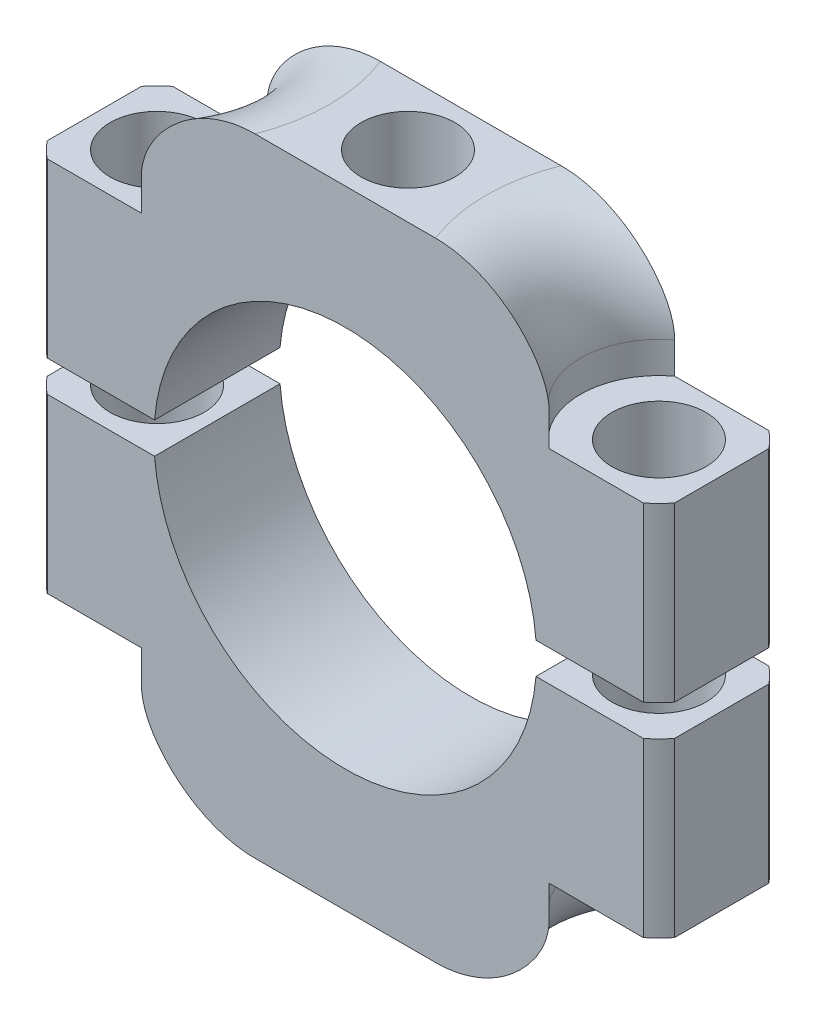
SolidWorks part; units mm, degrees
ref_plane "Front Plane" through (0, 0, 0) normal (0, 0, 1) x (1, 0, 0)
ref_plane "Top Plane" through (0, 0, 0) normal (0, 1, 0) x (1, 0, 0)
ref_plane "Right Plane" through (0, 0, 0) normal (1, 0, 0) x (0, 0, -1)
sketch "Sketch1" plane through (0, 0, 0) normal (0, 0, 1) x (1, 0, 0)
  line L1 (-10, -10) -> (10, -10)
  line L2 (-10, -10) -> (-10, 10)
  line L3 (-10, 10) -> (10, 10)
  line L4 (10, -10) -> (10, 10)
  line L5 (-10, -10) -> (10, 10) construction
  line L6 (-10, 10) -> (10, -10) construction
  line L7 (-10, -0.5) -> (-6.0795, -0.5)
  line L8 (-10, -0.5) -> (-10, 0.5)
  line L9 (-10, 0.5) -> (-6.0795, 0.5)
  line L10 (-6.0795, -0.5) -> (-6.0795, 0.5)
  line L11 (6.0795, -0.5) -> (10, -0.5)
  line L12 (6.0795, -0.5) -> (6.0795, 0.5)
  line L13 (6.0795, 0.5) -> (10, 0.5)
  line L14 (10, -0.5) -> (10, 0.5)
  circle A0 centre (0, 0) radius 6.1
  point P0 (0, 0)
  point P12 (6.0795, 0)
  point P13 (-6.0795, 0)
  dimension "D3" = 12.2
  dimension "D1" = 20
  dimension "D2" = 20
  dimension "D4" = 1
  dimension "D5" = 1
extrude "Boss-Extrude1" add sketch "Sketch1" along normal blind 4 contours A0 L7 L2 L1 L4 L11 | A0 L13 L4 L3 L2 L9 region at (0, -6.1587, 0) region at (0, 6.1587, 0)
sketch "Sketch2" plane through (0, 0, 0) normal (0, 1, 0) x (1, 0, 0)
  line L0 (10, -4) -> (10, 0) construction
  line L1 (-10, -4) -> (-10, 0) construction
  line L2 (0, 5.2223) -> (0, -8.4062) construction
  line L3 (-2.6121, 0) -> (-2.6121, -4)
  line L4 (-14.9471, -1.5628) -> (14.9628, -1.5628) construction
  line L5 (-10, 0) -> (10, 0) construction
  line L6 (-10, -4) -> (10, -4) construction
  circle A0 centre (8, -2) radius 2.5
  circle A1 centre (-8, -2) radius 2.5
  circle A2 centre (8, -2) radius 1.5
  circle A3 centre (-8, -2) radius 1.5
  point P21 (0, 0)
  point P22 (0, 0)
  dimension "D1" = 5
  dimension "D2" = 5
  dimension "D3" = 3
  dimension "D4" = 3
  dimension "D6" = 2
  dimension "D5" = 2
  dimension "D7" = 2
extrude "Cut-Extrude1" cut sketch "Sketch2" along direction (0, 1, 0) on the side of the normal blind 4 from surface contours A1 | A0 | A3 starting at face at (0, -10, 2)
sketch "Sketch3" plane through (0, 0, 0) normal (0, 1, 0) x (1, 0, 0)
  line L0 (0, 0) -> (0, -4)
  line L1 (-10, 0) -> (10, 0) construction
  line L2 (-10, -4) -> (-10, 0) construction
  line L3 (10, -4) -> (10, 0) construction
  circle A0 centre (8, -2) radius 2.5
  circle A1 centre (-8, -2) radius 2.5
  circle A2 centre (8, -2) radius 1.5
  circle A3 centre (-8, -2) radius 1.5
  point P8 (0, 0)
  point P11 (0, 0)
  point P12 (0, 0)
  point P13 (0, -2)
  dimension "D1" = 5
  dimension "D2" = 5
  dimension "D3" = 3
  dimension "D4" = 3
  dimension "D5" = 2
  dimension "D6" = 2
  dimension "D7" = 4
extrude "Cut-Extrude2" cut sketch "Sketch3" against normal blind 4 from surface contours A1 A3 | A0 A2 region at (5.5707, 0, 2) region at (-10.4293, 0, 2) starting at face at (0, 10, 2)
sketch "Sketch4" plane through (0, 10, 0) normal (0, 1, 0) x (1, 0, 0)
  line L0 (-10, -3.5) -> (-10, -4) construction
  line L1 (-10, -4) -> (-9.5, -4) construction
  line L2 (-9.5, 0) -> (-10, 0) construction
  line L3 (-10, 0) -> (-10, -0.5) construction
  line L4 (10, -0.5) -> (10, 0) construction
  line L5 (10, 0) -> (9.5, 0) construction
  line L6 (9.5, -4) -> (10, -4) construction
  line L7 (10, -4) -> (10, -3.5) construction
  line L8 (-10, -3.5) -> (-10, -4)
  line L9 (-10, -4) -> (-9.5, -4)
  line L10 (-9.5, 0) -> (-10, 0)
  line L11 (-10, 0) -> (-10, -0.5)
  line L12 (10, -0.5) -> (10, 0)
  line L13 (10, 0) -> (9.5, 0)
  line L14 (9.5, -4) -> (10, -4)
  line L15 (10, -4) -> (10, -3.5)
  circle A0 centre (8, -2) radius 1.5 construction
  circle A1 centre (-8, -2) radius 1.5 construction
  circle A2 centre (8, -2) radius 1.5
  circle A3 centre (-8, -2) radius 1.5
  arc A4 (-10, -3.5) -> (-9.5, -4) centre (-8, -2) ccw construction
  arc A5 (-9.5, 0) -> (-10, -0.5) centre (-8, -2) ccw construction
  arc A6 (10, -0.5) -> (9.5, 0) centre (8, -2) ccw construction
  arc A7 (9.5, -4) -> (10, -3.5) centre (8, -2) ccw construction
  arc A8 (-10, -3.5) -> (-9.5, -4) centre (-8, -2) ccw
  arc A9 (-9.5, 0) -> (-10, -0.5) centre (-8, -2) ccw
  arc A10 (10, -0.5) -> (9.5, 0) centre (8, -2) ccw
  arc A11 (9.5, -4) -> (10, -3.5) centre (8, -2) ccw
extrude "Cut-Extrude3" cut sketch "Sketch4" against normal through all
sketch "Sketch5" plane through (0, 10, 0) normal (0, 1, 0) x (1, 0, 0)
  line L0 (-6.5, -4) -> (6.5, -4) construction
  circle A0 centre (0, -2) radius 1.5
  point P5 (0, 0)
  dimension "D1" = 3
  dimension "D2" = 2
extrude "Cut-Extrude4" cut sketch "Sketch5" against normal blind 6
fillet "Fillet1" radius 3 2 edges at (5.5, 10, 2) (-5.5, 10, 2)
fillet "Fillet2" radius 3 2 edges at (5.5, -10, 2) (-5.5, -10, 2)
